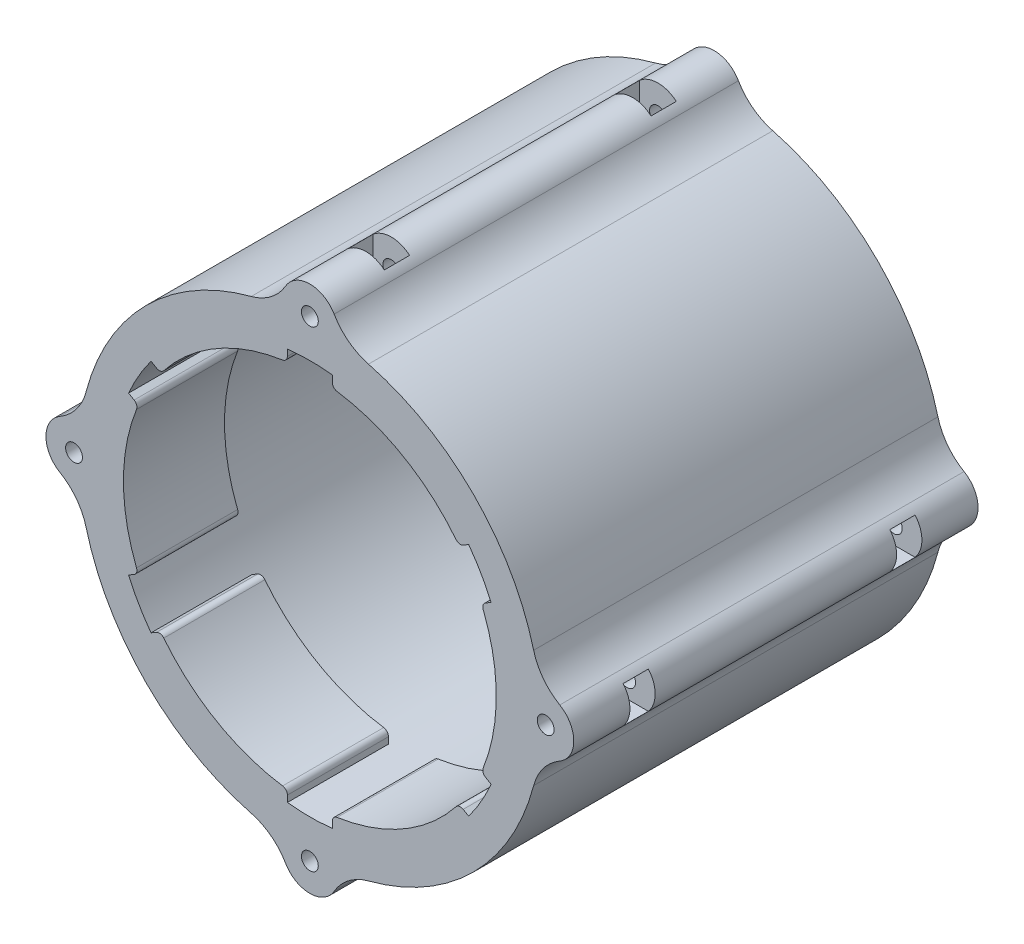
SolidWorks part; units mm, degrees
ref_plane "Ön Düzlem" through (0, 0, 0) normal (0, 0, 1) x (1, 0, 0)
ref_plane "Üst Düzlem" through (0, 0, 0) normal (0, 1, 0) x (1, 0, 0)
ref_plane "Sağ Düzlem" through (0, 0, 0) normal (1, 0, 0) x (0, 0, -1)
sketch "Çizim1" plane through (0, 0, 0) normal (0, 0, 1) x (1, 0, 0)
  circle A0 centre (0, 0) radius 35.2
  arc A1 (-39.8554, -10.4397) -> (-10.4397, -39.8554) centre (0, 0) ccw
  circle A6 centre (-42, 0) radius 1.5
  arc A7 (-44.5097, 4.3245) -> (-44.5097, -4.3245) centre (-42, 0) ccw
  circle A8 centre (0, 0) radius 41.2 construction
  arc A9 (-39.8554, -10.4397) -> (-44.5097, -4.3245) centre (-49.529, -12.9736) ccw
  arc A10 (-39.8554, 10.4397) -> (-44.5097, 4.3245) centre (-49.529, 12.9736) cw
  circle A11 centre (0, 42) radius 1.5
  arc A12 (4.3245, 44.5097) -> (-4.3245, 44.5097) centre (0, 42) ccw
  arc A13 (-10.4397, 39.8554) -> (-4.3245, 44.5097) centre (-12.9736, 49.529) ccw
  arc A14 (10.4397, 39.8554) -> (4.3245, 44.5097) centre (12.9736, 49.529) cw
  circle A15 centre (42, 0) radius 1.5
  arc A16 (44.5097, -4.3245) -> (44.5097, 4.3245) centre (42, 0) ccw
  arc A17 (39.8554, 10.4397) -> (44.5097, 4.3245) centre (49.529, 12.9736) ccw
  arc A18 (39.8554, -10.4397) -> (44.5097, -4.3245) centre (49.529, -12.9736) cw
  circle A19 centre (0, -42) radius 1.5
  arc A20 (-4.3245, -44.5097) -> (4.3245, -44.5097) centre (0, -42) ccw
  arc A21 (10.4397, -39.8554) -> (4.3245, -44.5097) centre (12.9736, -49.529) ccw
  arc A22 (-10.4397, -39.8554) -> (-4.3245, -44.5097) centre (-12.9736, -49.529) cw
  arc A23 (-10.4397, 39.8554) -> (-39.8554, 10.4397) centre (0, 0) ccw
  arc A24 (39.8554, 10.4397) -> (10.4397, 39.8554) centre (0, 0) ccw
  arc A25 (10.4397, -39.8554) -> (39.8554, -10.4397) centre (0, 0) ccw
  point P16 (0, 0)
  point P41 (0, 0)
  dimension "D1" = 70.4
  dimension "D3" = 5
  dimension "D4" = 3
  dimension "D5" = 42
  dimension "D6" = 10
  dimension "D2" = 6
  dimension "D7" = 4
extrude "Yükseklik-Ekstrüzyon1" add sketch "Çizim1" along normal blind 72
sketch "Çizim2" plane through (0, 0, 72) normal (0, 0, 1) x (1, 0, 0)
  line L0 (-4, 34.972) -> (-4, 32.9582)
  line L1 (4, 34.972) -> (4, 32.9582)
  line L2 (28.2866, 20.9501) -> (26.5426, 19.9432)
  line L3 (32.2866, 14.0219) -> (30.5426, 13.015)
  line L4 (32.2866, -14.0219) -> (30.5426, -13.015)
  line L5 (28.2866, -20.9501) -> (26.5426, -19.9432)
  line L6 (4, -34.972) -> (4, -32.9582)
  line L7 (-4, -34.972) -> (-4, -32.9582)
  line L8 (-28.2866, -20.9501) -> (-26.5426, -19.9432)
  line L9 (-32.2866, -14.0219) -> (-30.5426, -13.015)
  line L10 (-32.2866, 14.0219) -> (-30.5426, 13.015)
  line L11 (-28.2866, 20.9501) -> (-26.5426, 19.9432)
  arc A3 (-4, 34.972) -> (-28.2866, 20.9501) centre (0, 0) ccw
  arc A29 (-30.5426, 13.015) -> (-30.5426, -13.015) centre (0, 0) ccw
  arc A30 (-4, 32.9582) -> (-26.5426, 19.9432) centre (0, 0) ccw
  arc A31 (28.2866, 20.9501) -> (4, 34.972) centre (0, 0) ccw
  arc A34 (32.2866, -14.0219) -> (32.2866, 14.0219) centre (0, 0) ccw
  arc A36 (4, -34.972) -> (28.2866, -20.9501) centre (0, 0) ccw
  arc A38 (-28.2866, -20.9501) -> (-4, -34.972) centre (0, 0) ccw
  arc A40 (-32.2866, 14.0219) -> (-32.2866, -14.0219) centre (0, 0) ccw
  arc A41 (26.5426, 19.9432) -> (4, 32.9582) centre (0, 0) ccw
  arc A42 (30.5426, -13.015) -> (30.5426, 13.015) centre (0, 0) ccw
  arc A43 (4, -32.9582) -> (26.5426, -19.9432) centre (0, 0) ccw
  arc A44 (-26.5426, -19.9432) -> (-4, -32.9582) centre (0, 0) ccw
  point P55 (0, 0)
  dimension "D2" = 2
  dimension "D1" = 70.4
  dimension "D3" = 4
  dimension "D5" = 4
  dimension "D8" = 6
extrude "Yükseklik-Ekstrüzyon2" add sketch "Çizim2" against normal blind 18
ref_plane "Düzlem1" through (0, 0, 10) normal (0, 0, -1) x (-1, 0, 0)
sketch "Çizim3" plane through (0, 0, 10) normal (0, 0, -1) x (-1, 0, 0)
  line L0 (-3.262, -42) -> (-3.262, -48)
  line L1 (3.262, -42) -> (1.631, -39.175)
  line L2 (1.631, -39.175) -> (-1.631, -39.175)
  line L3 (-1.631, -39.175) -> (-3.262, -42)
  line L7 (3.262, -42) -> (3.262, -48)
  line L8 (3.262, -48) -> (-3.262, -48)
  line L9 (-2.4465, -43.4125) -> (-1.631, -44.825) [skipped]
  line L10 (0, -44.825) -> (1.631, -44.825) [skipped]
  line L11 (2.4465, -43.4125) -> (3.262, -42) [skipped]
  circle A0 centre (0, -42) radius 2.825 construction
  dimension "D1" = 3.262
  dimension "D2" = 6
  dimension "D3" = 6
  dimension "D4" = 3.262
  dimension "D5" = 3.262
extrude "Kes-Ekstrüzyon1" cut sketch "Çizim3" against normal blind 4.5
pattern_circular "Dairesel Kaplama1" count 4 every 90 about axis through (0, 0, 0) along (0, 0, 1) of "Kes-Ekstrüzyon1"
ref_plane "Düzlem2" through (0, 0, 36) normal (0, 0, -1) x (-1, 0, 0)
mirror "Aynalama1" about plane through (0, 0, 36) normal (0, 0, -1) of "Dairesel Kaplama1"
fillet "Radyus1" radius 1 12 edges at (4, 32.9582, 63) (-4, 32.9582, 63) (26.5426, -19.9432, 63) (30.5426, -13.015, 63) (-4, -32.9582, 63) (4, -32.9582, 63) (-26.5426, -19.9432, 63) (-30.5426, -13.015, 63) (-30.5426, 13.015, 63) (-26.5426, 19.9432, 63) (30.5426, 13.015, 63) (26.5426, 19.9432, 63)
